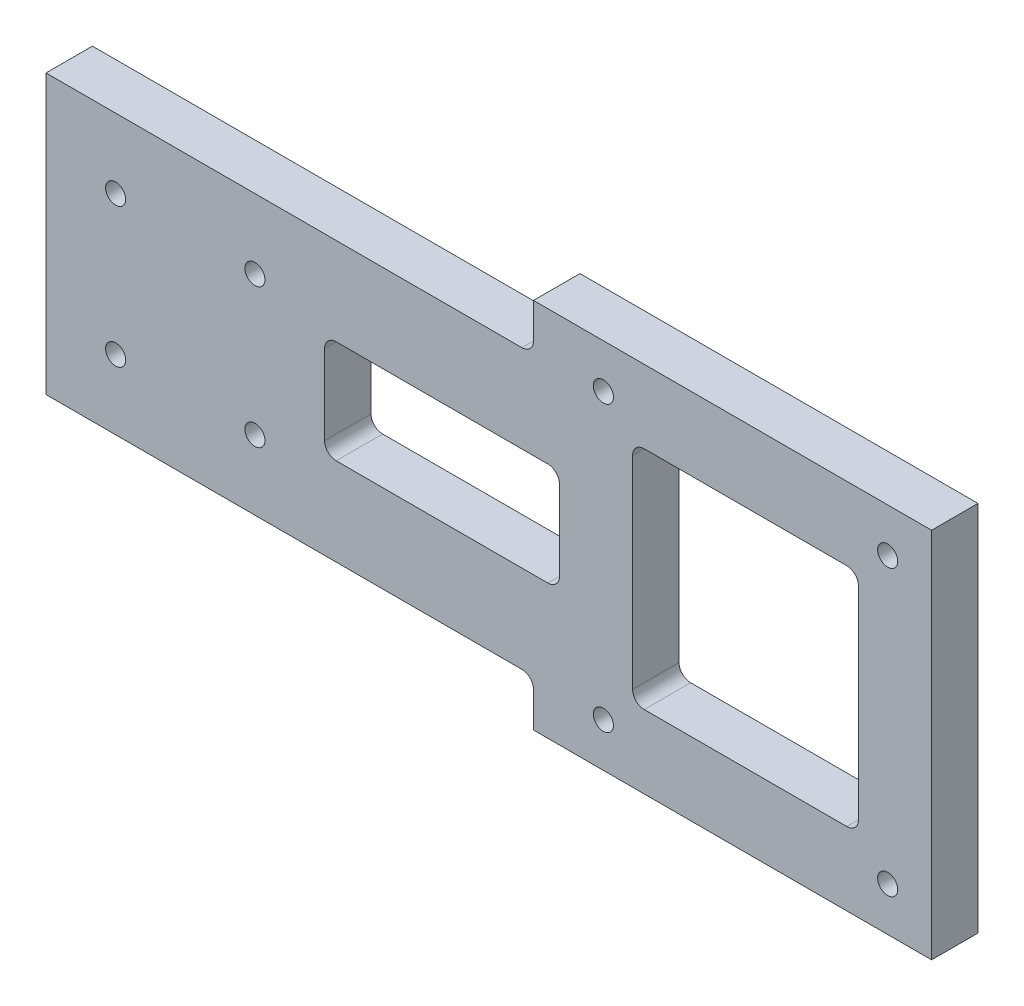
SolidWorks part; units mm, degrees
material "6061-T6 (SS)"
ref_plane "Front" through (0, 0, 0) normal (0, 0, 1) x (1, 0, 0)
ref_plane "Top" through (0, 0, 0) normal (0, 1, 0) x (1, 0, 0)
ref_plane "Right" through (0, 0, 0) normal (1, 0, 0) x (0, 0, -1)
sketch "Sketch1" plane through (0, 0, 0) normal (0, 0, 1) x (1, 0, 0)
  line L0 (95.25, 38.1) -> (95.25, 50.8909)
  line L1 (95.25, 38.1) -> (-38.1, 38.1)
  line L3 (95.25, -38.1) -> (-38.1, -38.1)
  line L4 (-38.1, 38.1) -> (-38.1, -38.1)
  line L5 (-38.1, -38.1) -> (0, 0) construction
  line L6 (0, 0) -> (-38.1, 38.1) construction
  line L7 (95.25, 50.8909) -> (204.1409, 50.8909)
  line L8 (204.1409, 50.8909) -> (204.1409, 30.8909)
  line L9 (204.1409, 30.8909) -> (122.3591, 30.8909)
  line L10 (122.3591, 30.8909) -> (122.3591, -30.8909)
  line L11 (122.3591, -30.8909) -> (204.1409, -30.8909)
  line L12 (204.1409, -30.8909) -> (204.1409, -50.8909)
  line L13 (204.1409, -50.8909) -> (95.25, -50.8909)
  line L14 (95.25, -50.8909) -> (95.25, -38.1)
  line L15 (192.1409, -30.8909) -> (192.1409, -38.8909) construction
  line L16 (192.1409, -38.8909) -> (192.1409, -50.8909) construction
  line L17 (0, 0) -> (153.25, 0) construction
  line L18 (192.1409, -38.8909) -> (114.3591, 38.8909) construction
  line L19 (192.1409, 38.8909) -> (114.3591, -38.8909) construction
  line L20 (122.3591, 30.8909) -> (153.25, 0) construction
  line L21 (153.25, 0) -> (122.3591, -30.8909) construction
  line L22 (192.1409, 38.8909) -> (192.1409, 50.8909) construction
  line L23 (192.1409, 38.8909) -> (204.1409, 38.8909) construction
  line L24 (192.1409, 38.8909) -> (192.1409, 30.8909) construction
  line L25 (114.3591, 38.8909) -> (95.25, 38.8909) construction
  line L26 (0, 0) -> (122.3591, 0) construction
  line L27 (0, 0) -> (95.25, -38.1) construction
  line L28 (0, 0) -> (95.25, 38.1) construction
  line L29 (192.1409, -38.8909) -> (204.1409, -38.8909) construction
  line L30 (153.25, 0) -> (153.25, 30.8909) construction
  line L31 (153.25, 0) -> (122.3591, 0) construction
  circle A0 centre (153.25, 0) radius 55 construction
  point P0 (0, 0)
  point P17 (192.1409, 38.8909)
  point P18 (192.1409, -38.8909)
  point P19 (114.3591, 38.8909)
  point P20 (114.3591, -38.8909)
  dimension "D2" = 110
  dimension "D1" = 76.2
  dimension "D3" = 90
  dimension "D5" = 8
  dimension "D6" = 12
  dimension "D7" = 133.35
  dimension "D9" = 58
  dimension "D10" = 0
extrude "Boss-Extrude1" add sketch "Sketch1" along normal blind 12.7
hole_wizard "M5 Clearance Hole1" positions "Sketch3" profile "Sketch4" hole size "M5" standard "ANSI Metric"
sketch "Sketch3" plane through (0, 0, 12.7) normal (0, 0, 1) x (1, 0, 0)
  line L0 (0, 0) -> (153.25, 0) construction
  line L2 (192.1409, -38.8909) -> (114.3591, 38.8909) construction
  line L4 (192.1409, 38.8909) -> (114.3591, -38.8909) construction
  line L6 (122.3591, 30.8909) -> (153.25, 0) construction
  line L7 (153.25, 0) -> (122.3591, -30.8909) construction
  line L8 (95.25, 38.1) -> (-38.1, 38.1) construction
  line L12 (95.25, -38.1) -> (95.25, -50.8909) construction
  circle A0 centre (153.25, 0) radius 55 construction
  point P0 (192.1409, 38.8909)
  point P2 (192.1409, -38.8909)
  point P4 (114.3591, 38.8909)
  point P6 (114.3591, -38.8909)
  dimension "D1" = 110
  dimension "D2" = 135
  dimension "D3" = 90
  dimension "D4" = 58
sketch "Sketch4" plane through (192.1409, 38.8909, 12.7) normal (1, 0, 0) x (0, -1, 0)
  line L0 (0, 0) -> (0, 20.4024)
  line L1 (0, 20.4024) -> (2.75, 18.75)
  line L2 (2.75, 18.75) -> (2.75, 0)
  line L5 (2.75, 0) -> (0, 0)
  line L10 (0, 20.4024) -> (-2.75, 18.75) construction
  line L11 (0, -6.35) -> (0, 107.95) construction
  dimension "Hole Dia." = 5.5
  dimension "Hole Depth" = 18.75
  dimension "Drill Angle" = 118
fillet "Fillet1" radius 3.175 4 edges at (122.3591, 30.8909, 6.35) (122.3591, -30.8909, 6.35) (95.25, -38.1, 6.35) (95.25, 38.1, 6.35)
hole_wizard "M5 Clearance Hole2" positions "Sketch5" profile "Sketch6" hole size "M5" standard "ANSI Metric"
sketch "Sketch5" plane through (0, 0, 12.7) normal (0, 0, 1) x (1, 0, 0)
  line L0 (-19.05, 19.05) -> (19.05, 19.05) construction
  line L1 (19.05, 19.05) -> (19.05, -19.05) construction
  line L2 (19.05, -19.05) -> (-19.05, -19.05) construction
  line L3 (-19.05, -19.05) -> (-19.05, 19.05) construction
  line L5 (92.075, 38.1) -> (-38.1, 38.1) construction
  line L9 (-38.1, -38.1) -> (-19.05, -19.05) construction
  line L11 (-19.05, 19.05) -> (-38.1, 38.1) construction
  point P0 (-19.05, 19.05)
  point P2 (19.05, 19.05)
  point P4 (19.05, -19.05)
  point P6 (-19.05, -19.05)
  dimension "D1" = 19.05
  dimension "D2" = 38.1
sketch "Sketch6" plane through (-19.05, 19.05, 12.7) normal (1, 0, 0) x (0, -1, 0)
  line L0 (0, 0) -> (0, 20.4024)
  line L1 (0, 20.4024) -> (2.75, 18.75)
  line L2 (2.75, 18.75) -> (2.75, 0)
  line L5 (2.75, 0) -> (0, 0)
  line L10 (0, 20.4024) -> (-2.75, 18.75) construction
  line L11 (0, -6.35) -> (0, 107.95) construction
  dimension "Hole Dia." = 5.5
  dimension "Hole Depth" = 18.75
  dimension "Drill Angle" = 118
sketch "Sketch7" plane through (0, 0, 12.7) normal (0, 0, 1) x (1, 0, 0)
  line L0 (19.05, 19.05) -> (19.05, 38.1) construction
  line L1 (102.3591, -14.1) -> (38.1, -14.1)
  line L2 (102.3591, -14.1) -> (102.3591, 14.1)
  line L3 (102.3591, 14.1) -> (38.1, 14.1)
  line L4 (38.1, -14.1) -> (38.1, 14.1)
  line L5 (102.3591, -14.1) -> (38.1, 14.1) construction
  line L6 (102.3591, 14.1) -> (38.1, -14.1) construction
  line L7 (122.3591, -27.7159) -> (122.3591, 27.7159) construction
  line L8 (92.075, 38.1) -> (-38.1, 38.1) construction
  line L9 (0, 0) -> (70.2296, 0) construction
  line L10 (19.05, 19.05) -> (38.1, 19.05) construction
  point P0 (70.2296, 0)
  dimension "D1" = 20
  dimension "D2" = 24
extrude "Cut-Extrude1" cut sketch "Sketch7" against normal through all
fillet "Fillet2" radius 3.175 4 edges at (102.3591, -14.1, 6.35) (102.3591, 14.1, 6.35) (38.1, 14.1, 6.35) (38.1, -14.1, 6.35)
sketch "Sketch8" plane through (0, 0, 12.7) normal (0, 0, 1) x (1, 0, 0)
  line L0 (125.5341, 30.8909) -> (204.1409, 30.8909) construction
  line L1 (204.1409, -30.8909) -> (184.1409, -30.8909)
  line L2 (204.1409, -30.8909) -> (204.1409, 30.8909)
  line L3 (204.1409, 30.8909) -> (184.1409, 30.8909)
  line L4 (184.1409, -30.8909) -> (184.1409, 30.8909)
  line L5 (204.1409, -50.8909) -> (204.1409, -30.8909) construction
extrude "Boss-Extrude2" add sketch "Sketch8" against normal up to surface (12.7 mm away) up to face at (70.2296, 0, 0)
fillet "Fillet3" radius 3.175 2 edges at (184.1409, -30.8909, 6.35) (184.1409, 30.8909, 6.35)
